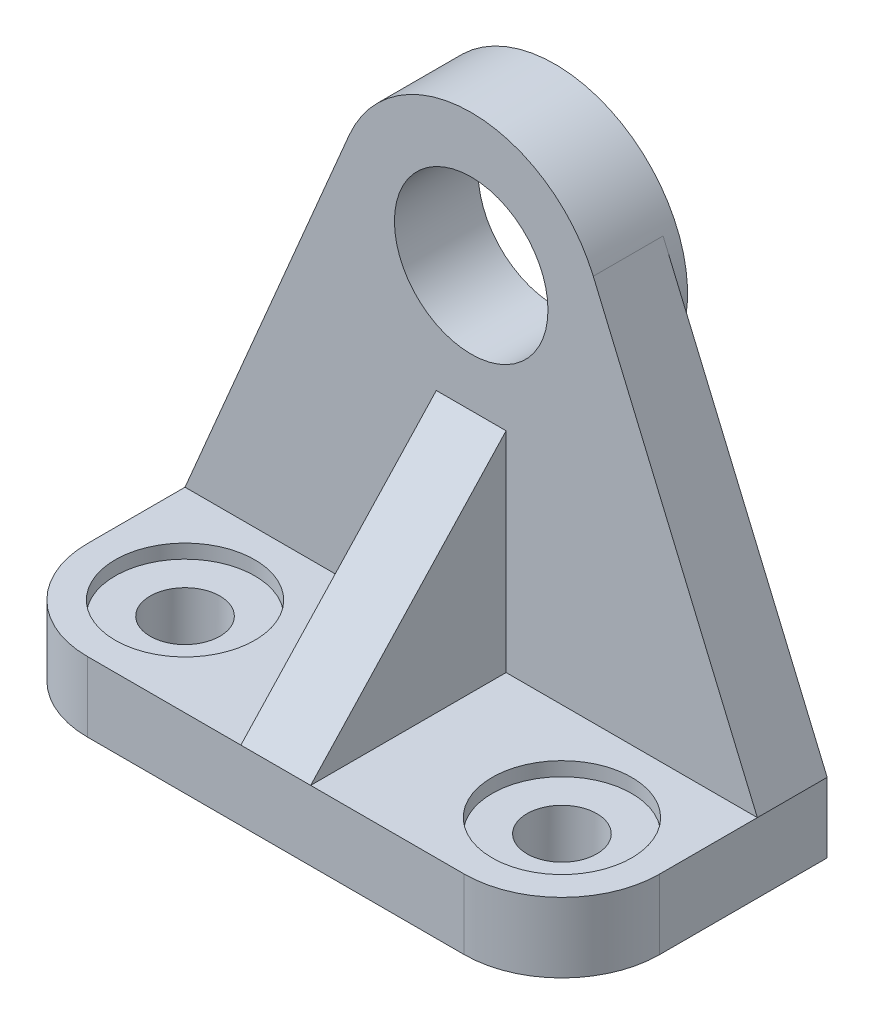
SolidWorks part; units mm, degrees
ref_plane "Front Plane" through (0, 0, 0) normal (0, 0, 1) x (1, 0, 0)
ref_plane "Top Plane" through (0, 0, 0) normal (0, 1, 0) x (1, 0, 0)
ref_plane "Right Plane" through (0, 0, 0) normal (1, 0, 0) x (0, 0, -1)
sketch "Sketch1" plane through (0, 0, 0) normal (0, 1, 0) x (1, 0, 0)
  line L1 (0, 0) -> (-41, 0)
  line L2 (0, 0) -> (0, -38)
  line L3 (0, -38) -> (-41, -38)
  line L4 (-41, 0) -> (-41, -38)
  dimension "D1" = 38
  dimension "D2" = 41
extrude "Boss-Extrude1" add sketch "Sketch1" along normal blind 10
sketch "Sketch2" plane through (0, 10, 0) normal (0, 1, 0) x (1, 0, 0)
  line L2 (-41, -38) -> (0, -38) construction
  line L3 (-41, 0) -> (-41, -38) construction
  circle A0 centre (-27, -24) radius 5
  circle A1 centre (-27, -24) radius 10
  point P7 (-30.2997, 2.4871)
  point P8 (-27.7293, -18.5582)
  dimension "D1" = 20
  dimension "D2" = 10
  dimension "D3" = 14
  dimension "D4" = 14
extrude "Cut-Extrude1" cut sketch "Sketch2" against normal blind 2
extrude "Cut-Extrude2" cut sketch "Sketch2<2>" against normal up to next contours A0 region at (-27, 10, 24)
sketch "Sketch2<2>" plane through (0, 10, 0) normal (0, 1, 0) x (1, 0, 0) same geometry as "Sketch2"
fillet "Fillet1" radius 14 1 edges at (-41, 5, 38)
sketch "Sketch4" plane through (0, 0, 0) normal (0, 0, 1) x (1, 0, 0)
  line L0 (-17.4914, 65.4197) -> (-41, 10)
  line L1 (0, 10) -> (0, 0) construction
  line L2 (0, 58) -> (0, 0) construction
  line L3 (0, 10) -> (0, 77)
  line L5 (0, 10) -> (-41, 10) construction
  line L6 (0, 10) -> (-41, 10)
  arc A0 (0, 77) -> (-17.4914, 65.4197) centre (0, 58) ccw
  arc A1 (0, 69) -> (0, 47) centre (0, 58) ccw
  dimension "D1" = 22
  dimension "D2" = 38
  dimension "D3" = 58
extrude "Boss-Extrude2" add sketch "Sketch4" along normal blind 10 contours A1 L3 A0 L0 L6 region at (-15.9197, 34.4614, 0)
sketch "Sketch5" plane through (0, 0, 0) normal (0, 0, -1) x (-1, 0, 0)
  line L5 (0, 0) -> (41, 0)
  line L6 (41, 0) -> (41, 10)
  line L7 (41, 10) -> (17.4914, 65.4197)
  line L8 (0, 77) -> (0, 69)
  line L9 (0, 47) -> (0, 0)
  line L10 (0, 0) -> (41, 0)
  line L11 (41, 0) -> (41, 10)
  line L12 (41, 10) -> (17.4914, 65.4197)
  line L13 (0, 77) -> (0, 69)
  line L14 (0, 47) -> (0, 0)
  circle A0 centre (0, 58) radius 19
  arc A2 (17.4914, 65.4197) -> (0, 77) centre (0, 58) ccw
  arc A3 (0, 47) -> (0, 69) centre (0, 58) ccw
  arc A4 (17.4914, 65.4197) -> (0, 77) centre (0, 58) ccw
  arc A5 (0, 47) -> (0, 69) centre (0, 58) ccw
  arc M12 (17.4914, 65.4197) -> (0, 77) centre (0, 58) ccw
  line M13 (0, 77) -> (0, 69)
  arc M14 (0, 69) -> (0, 47) centre (0, 58) cw
  line M15 (0, 47) -> (0, 0)
  dimension "D1" = 0
extrude "Boss-Extrude3" add sketch "Sketch5" along normal blind 2 contours A0 M15 M12 M13 M14 region at (-0.4249, 43, 0)
sketch "Sketch6" plane through (0, 0, 0) normal (1, 0, 0) x (0, 0, -1)
  line L0 (-38, 10) -> (-10, 40)
  line L8 (-38, 0) -> (0, 0)
  line L9 (0, 0) -> (0, 39)
  line L10 (0, 39) -> (2, 39)
  line L11 (2, 39) -> (2, 47)
  line L12 (2, 47) -> (-10, 47)
  line L13 (-10, 47) -> (-10, 10)
  line L14 (-10, 10) -> (-38, 10)
  line L15 (-38, 10) -> (-38, 0)
  line L21 (-10, 40) -> (-10, 10)
  line L22 (-10, 10) -> (-38, 10)
  dimension "D2" = 30
  dimension "D1" = 0
extrude "Boss-Extrude4" add sketch "Sketch6" against normal blind 5
mirror "Mirror1" about plane through (0, 10, 0) normal (-1, 0, 0) of bodies 106
